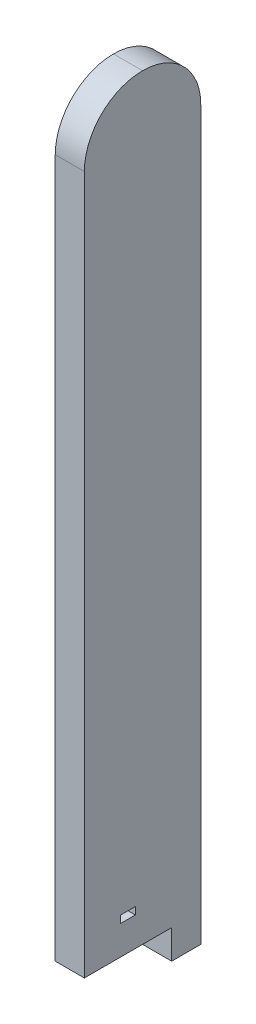
SolidWorks part; units mm, degrees
ref_plane "Front Plane" through (0, 0, 0) normal (0, 0, 1) x (1, 0, 0)
ref_plane "Top Plane" through (0, 0, 0) normal (0, 1, 0) x (1, 0, 0)
ref_plane "Right Plane" through (0, 0, 0) normal (1, 0, 0) x (0, 0, -1)
sketch "Sketch1" plane through (0, 0, 0) normal (1, 0, 0) x (0, 0, -1)
  line L0 (12.7, -69.5376) -> (12.7, -158.75)
  line L1 (-12.7, 12.7) -> (12.7, 12.7)
  line L2 (-12.7, 12.7) -> (-12.7, -152.4)
  line L3 (-12.7, -152.4) -> (6.35, -152.4)
  line L4 (12.7, 12.7) -> (12.7, -69.5376)
  line L5 (133.7662, -172.1141) -> (-245.2707, -128.1982) construction
  line L7 (12.7, -158.75) -> (6.35, -158.75)
  line L8 (6.35, -158.75) -> (6.35, -152.4)
  line L9 (4.503, -155.575) -> (-49995.497, -155.575) construction
  line L11 (-12.7, 12.7) -> (0, 0) construction
  line L12 (0, 0) -> (12.7, 12.7) construction
  circle A0 centre (0, 0) radius 155.575 construction
  point P0 (0, 0)
  point P11 (6.35, -155.575)
  dimension "D1" = 25.4
  dimension "D2" = 6.35
  dimension "D3" = 6.35
extrude "Boss-Extrude1" add sketch "Sketch1" along normal mid plane 6.35
fillet "Fillet1" radius 12.7 2 edges at (0, 12.7, -12.7) (0, 12.7, 12.7)
sketch "Sketch2" plane through (3.175, 0, 0) normal (1, 0, 0) x (0, 0, -1)
  line L1 (-4.7625, -146.05) -> (-1.5875, -146.05)
  line L2 (-4.7625, -146.05) -> (-4.7625, -144.4625)
  line L3 (-4.7625, -144.4625) -> (-1.5875, -144.4625)
  line L4 (-1.5875, -146.05) -> (-1.5875, -144.4625)
  line L5 (-4.7625, -146.05) -> (-1.5875, -144.4625) construction
  line L6 (-4.7625, -144.4625) -> (-1.5875, -146.05) construction
  line L7 (-3.175, -152.4) -> (-3.175, -145.2563) construction
  line L8 (-12.7, -152.4) -> (6.35, -152.4) construction
  point P0 (-3.175, -145.2563)
  dimension "D1" = 6.35
  dimension "D2" = 1.5875
  dimension "D3" = 3.175
extrude "Cable-tie hole" cut sketch "Sketch2" against normal through all
